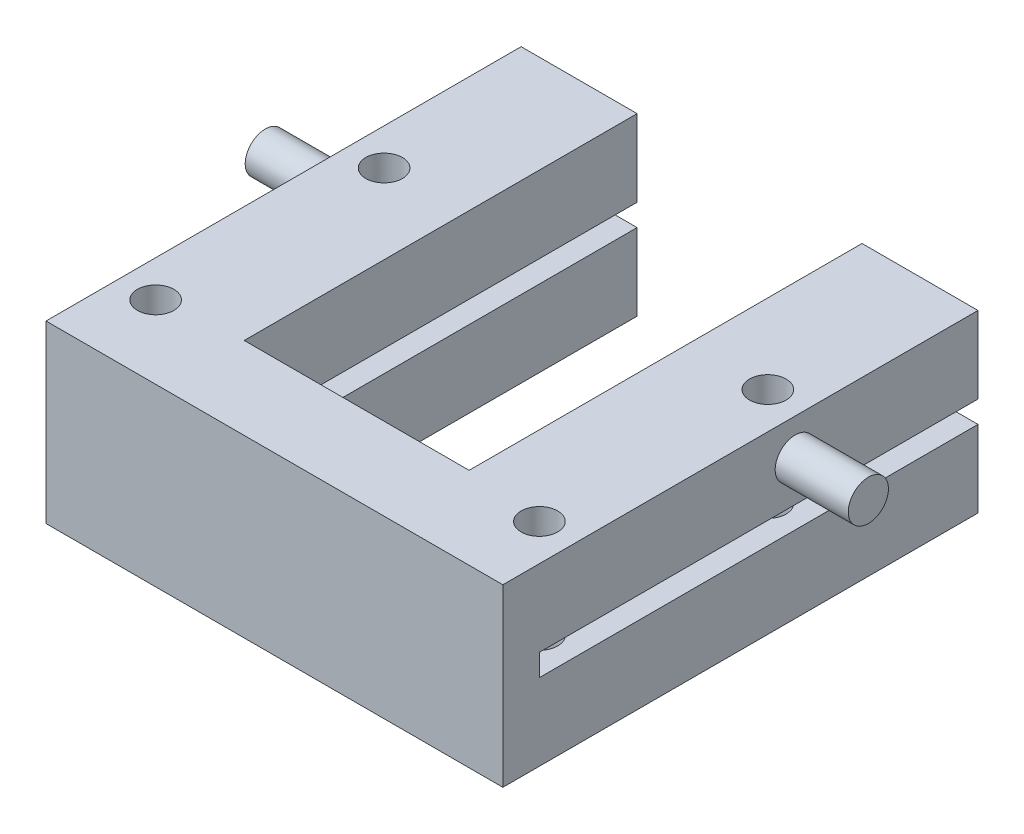
SolidWorks part; units mm, degrees
ref_plane "Front Plane" through (0, 0, 0) normal (0, 0, 1) x (1, 0, 0)
ref_plane "Top Plane" through (0, 0, 0) normal (0, 1, 0) x (1, 0, 0)
ref_plane "Right Plane" through (0, 0, 0) normal (1, 0, 0) x (0, 0, -1)
sketch "Sketch1" plane through (0, 0, 0) normal (0, 1, 0) x (1, 0, 0)
  line L0 (12.5, 24) -> (12.5, 0) construction
  line L1 (0, 0) -> (25, 0)
  line L2 (0, 0) -> (0, 24)
  line L3 (0, 24) -> (4.25, 24)
  line L4 (25, 0) -> (25, 24)
  line L5 (20.75, 24) -> (25, 24)
  line L7 (4.25, 24) -> (4.25, 2.5)
  line L8 (4.25, 2.5) -> (20.75, 2.5)
  line L9 (20.75, 24) -> (20.75, 2.5)
  circle A0 centre (2, 14.5) radius 1
  circle A1 centre (2, 2) radius 1
  circle A2 centre (23, 2) radius 1
  circle A3 centre (23, 14.5) radius 1
  dimension "D3" = 2
  dimension "D4" = 9.5
  dimension "D5" = 2
  dimension "D6" = 12.5
  dimension "D7" = 2
  dimension "D8" = 2
  dimension "D1" = 24
  dimension "D2" = 25
  dimension "D9" = 2.25
  dimension "D10" = 2.25
  dimension "D11" = 2.5
extrude "Boss-Extrude1" add sketch "Sketch1" along normal blind 4.2
sketch "Sketch2" plane through (0, 0, 0) normal (-1, 0, 0) x (0, 0, 1)
  line L0 (-24, 4.2) -> (0, 4.2) construction
  line L2 (0, 4.2) -> (0, 0) construction
  circle A0 centre (-14, 2.2) radius 1.1
  dimension "D1" = 2.2
  dimension "D2" = 2
  dimension "D3" = 14
extrude "Boss-Extrude2" add sketch "Sketch2" along normal blind 4
ref_plane "Plane1" through (12.5, 0, 0) normal (-1, 0, 0) x (0, 0, 1)
mirror "Mirror1" about plane through (12.5, 0, 0) normal (-1, 0, 0) of "Boss-Extrude2"
ref_plane "Plane2" through (0, -0.6, 0) normal (0, -1, 0) x (-1, 0, 0)
sketch "Sketch3" plane through (0, 0, 0) normal (0, 0, 1) x (1, 0, 0)
  line L0 (0, 4.2) -> (25, 4.2) construction
  line L1 (0, 4.2) -> (25, 4.2)
  line L2 (0, 4.2) -> (0, 0)
  line L3 (0, 0) -> (25, 0)
  line L4 (25, 4.2) -> (25, 0)
  line L5 (25, 4.2) -> (25, 0) construction
extrude "Boss-Extrude3" add sketch "Sketch3" along normal blind 2
sketch "Sketch4" plane through (0, 0, 0) normal (0, -1, 0) x (1, 0, 0)
  line L0 (0, -24) -> (0, 2) construction
  line L1 (0, 2) -> (25, 2)
  line L2 (0, 2) -> (0, 0)
  line L3 (0, 0) -> (25, 0)
  line L4 (25, 2) -> (25, 0)
  line L5 (25, 2) -> (25, -24) construction
  dimension "D1" = 2
extrude "Boss-Extrude4" add sketch "Sketch4" along normal blind 0.6
extrude "Boss-Extrude5" add sketch "Sketch1<3>" against normal blind 5.4
sketch "Sketch1<3>" plane through (0, 0, 0) normal (0, 1, 0) x (1, 0, 0) same geometry as "Sketch1"
extrude "Boss-Extrude6" add sketch "Sketch4<2>" along normal blind 5.4
sketch "Sketch4<2>" plane through (0, 0, 0) normal (0, -1, 0) x (1, 0, 0) same geometry as "Sketch4"
sketch "Sketch5" plane through (0, 0, -2.5) normal (0, 0, -1) x (-1, 0, 0)
  line L1 (-25, 0) -> (0, 0)
  line L2 (-25, 0) -> (-25, -1.2)
  line L3 (-25, -1.2) -> (0, -1.2)
  line L4 (0, 0) -> (0, -1.2)
  line L6 (-55, -0.6) -> (55, -0.6) construction
  line L7 (-12.5, -5.28) -> (-12.5, 5.28) construction
  point P6 (-12.5, 0)
  dimension "D1" = 1.2
  dimension "D2" = 0.6
  dimension "D3" = 25
extrude "Cut-Extrude2" cut sketch "Sketch5" along normal up to surface (21.5 mm away) up to face at (22.875, -0.6, -24)
sketch "Sketch6" plane through (0, 0, -2.5) normal (0, 0, -1) x (-1, 0, 0)
  line L1 (-20.75, 4.2) -> (-18.6536, 4.2)
  line L2 (-20.75, 4.2) -> (-20.75, 0)
  line L3 (-20.75, 0) -> (-18.6536, 0)
  line L4 (-18.6536, 4.2) -> (-18.6536, 0)
  line L5 (-12.5, -5.28) -> (-12.5, 5.28) construction
  line L6 (-4.25, 0) -> (-6.3464, 0)
  line L7 (-6.3464, 4.2) -> (-6.3464, 0)
  line L8 (-4.25, 4.2) -> (-6.3464, 4.2)
  line L9 (-4.25, 4.2) -> (-4.25, 0)
  line L10 (-55, -0.6) -> (55, -0.6) construction
  line L11 (-4.25, -5.4) -> (-4.25, -1.2)
  line L12 (-4.25, -5.4) -> (-6.3464, -5.4)
  line L13 (-6.3464, -5.4) -> (-6.3464, -1.2)
  line L14 (-4.25, -1.2) -> (-6.3464, -1.2)
  line L15 (-20.75, -1.2) -> (-18.6536, -1.2)
  line L16 (-18.6536, -5.4) -> (-18.6536, -1.2)
  line L17 (-20.75, -5.4) -> (-18.6536, -5.4)
  line L18 (-20.75, -5.4) -> (-20.75, -1.2)
  point P23 (0, 0)
extrude "Boss-Extrude8" add sketch "Sketch6" along normal up to surface (21.5 mm away) up to face at (22.875, 2.1, -24)
extrude "Cut-Extrude4" cut sketch "Sketch5<2>" against normal blind 2.5
sketch "Sketch5<2>" plane through (0, 0, -2.5) normal (0, 0, -1) x (-1, 0, 0) same geometry as "Sketch5"
